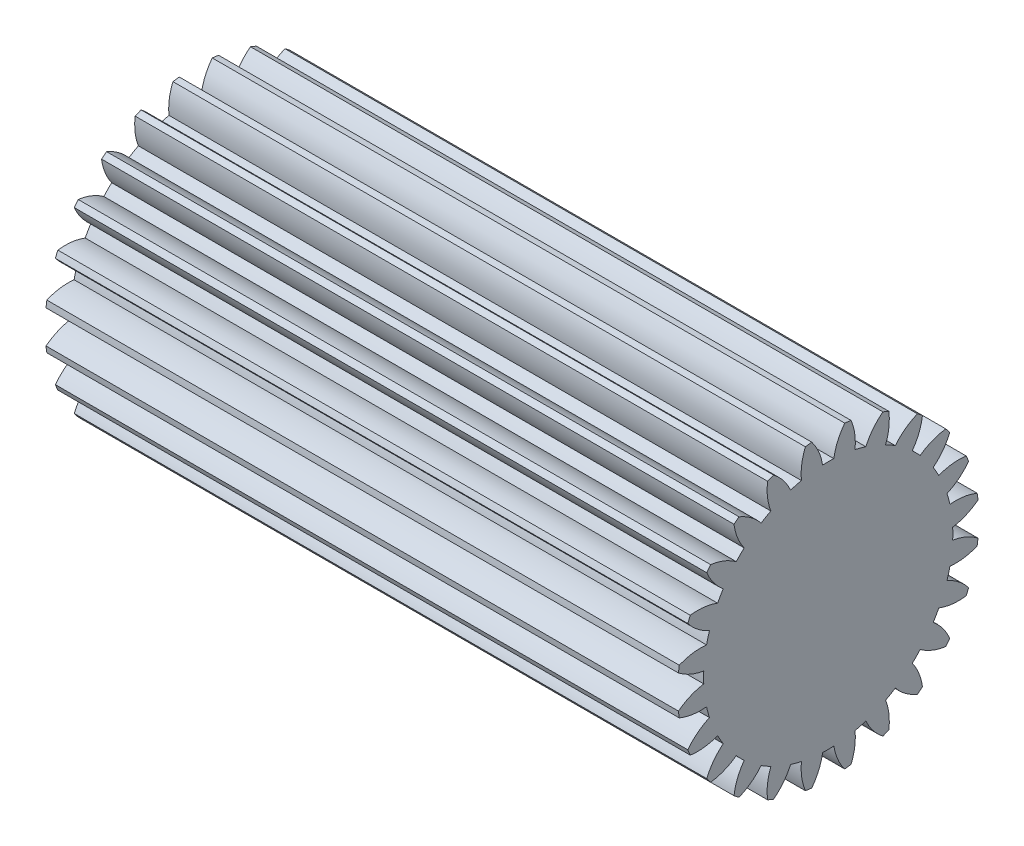
SolidWorks part; units mm, degrees
ref_plane "Plane1" through (0, 0, 0) normal (0, 0, 1) x (1, 0, 0)
ref_plane "Plane2" through (0, 0, 0) normal (0, 1, 0) x (1, 0, 0)
ref_plane "Plane3" through (0, 0, 0) normal (1, 0, 0) x (0, 0, -1)
sketch "HoldingSke" plane through (0, 0, 0) normal (0, 1, 0) x (1, 0, 0)
  line L0 (0, 0) -> (0.9135, -0.4067)
  line L1 (-15, 0) -> (100, 0) construction
  line L2 (0, 0) -> (-2.1039, 2.3779)
  line L3 (0, 0) -> (-11.863, 4.5341)
  line L4 (0, 0) -> (7.8894, 3.5126)
  line L5 (0, 0) -> (-46.8476, -17.4728)
  line L6 (0, 0) -> (-9.9476, -6.7116)
  line L7 (-2.1039, 2.3779) -> (8.6586, 51.2059)
  line L8 (-76.2, 54.61) -> (-76.1, 54.61)
  line L9 (-71.009, 38.7566) -> (-53.1078, 45.2721)
  line L10 (-76.2, 71.12) -> (104.1128, 71.12)
  line L11 (0, 0) -> (-12, 0)
  line L12 (-76.2, 101.6) -> (-76.162, 101.6)
  line L13 (24.9733, 27.94) -> (52.9518, 28.4284)
  line L14 (24.9733, 27.94) -> (24.9743, 27.94)
  line L15 (24.9733, 27.94) -> (100.4006, 29.5858)
  line L16 (-63.627, -1) -> (-12.827, -1)
  circle A0 centre (0, 0) radius 0.4
  circle A1 centre (0, 0) radius 10.749
  circle A2 centre (0, 0) radius 37.5
  circle A3 centre (0, 0) radius 0.4
  dimension "Num_teeth" = 24
  dimension "Pitch_radius" = 180.3128
  dimension "Width" = 12
sketch "BasProSke" plane through (0, 0, 0) normal (0, 1, 0) x (1, 0, 0)
  line L0 (-10, 0) -> (60, 0) construction
  line L1 (0, 0) -> (0, 13)
  line L2 (0, 0) -> (54.565, 0)
  line L3 (54.565, 0) -> (54.565, 13)
  line L4 (54.565, 13) -> (0, 13)
  dimension "Thickness" = 54.565
  dimension "Diameter" = 26
revolve "Base-Revolve" add sketch "BasProSke" angle 360 about L0
sketch "TooCutSke" plane through (0, 0, 0) normal (1, 0, 0) x (0, 0, -1)
  line L1 (0, 0) -> (0, 107) construction
  line L2 (0, 0) -> (-0.8513, 11.9698) construction
  line L3 (0, 0) -> (-3.127, 23.752) construction
  line L4 (-0.8513, 11.9698) -> (-1.5635, 11.876) construction
  arc A0 (0.4834, 10.7381) -> (-0.4834, 10.7381) centre (0, 0) ccw
  arc A1 (1.4409, 12.9455) -> (-1.4409, 12.9455) centre (0, 0) ccw
  circle A2 centre (0, 0) radius 12 construction
  circle A3 centre (0, 0) radius 11.2763 construction
  arc A4 (-0.4834, 10.7381) -> (-1.4409, 12.9455) centre (-5.2252, 9.9926) ccw
  arc A5 (1.4409, 12.9455) -> (0.4834, 10.7381) centre (5.2252, 9.9926) ccw
extrude "ToothCut" cut sketch "TooCutSke" along normal through all
fillet "Breaks" [suppressed] radius 0.02 tangent propagation no
fillet "RootFillets" [suppressed] radius 0.251
pattern_circular "TeethCuts" count 24 every 15 about axis through (-10, 0, 0) along (1, 0, 0) of "ToothCut", "RootFillets", "Breaks"
sketch "HubNeaOneSke" plane through (0, 0, 0) normal (-1, 0, 0) x (0, 0, 1)
  circle A0 centre (0, 0) radius 10.749
  dimension "Diameter" = 21.498
extrude "HubNearOne" [suppressed] add sketch "HubNeaOneSke" along normal blind 15.1851
sketch "HubNeaBotSke" plane through (0, 0, 0) normal (-1, 0, 0) x (0, 0, 1)
  circle A0 centre (0, 0) radius 10.749
  dimension "Diameter" = 21.498
extrude "HubNearBoth" [suppressed] add sketch "HubNeaBotSke" along normal blind 7.5925
ref_plane "FarPln" through (54.565, 0, 0) normal (1, 0, 0) x (0, 0, -1)
sketch "HubFarSke" plane through (54.565, 0, 0) normal (1, 0, 0) x (0, 0, -1)
  circle A0 centre (0, 0) radius 10.749
  dimension "Diameter" = 21.498
extrude "HubFar" [suppressed] add sketch "HubFarSke" along normal blind 7.5925
sketch "BorSke" plane through (0, 0, 0) normal (1, 0, 0) x (0, 0, -1)
  circle A0 centre (0, 0) radius 0.4
  dimension "Diameter" = 0.8
extrude "Bore" cut sketch "BorSke" along normal mid plane 100.0001
sketch "KeySke" plane through (0, 0, 0) normal (1, 0, 0) x (0, 0, -1)
  line L0 (-0.05, 0) -> (-0.05, 0.5)
  line L1 (-0.05, 0.5) -> (0.05, 0.5)
  line L2 (0.05, 0.5) -> (0.05, 0)
  line L3 (0, 0) -> (0, 34) construction
  line L4 (-0.05, 0) -> (0.05, 0)
  dimension "Width" = 0.1
extrude "Keyway" [suppressed] cut sketch "KeySke" along normal mid plane 100.0001
pattern_circular "Keyway2" [suppressed] count 2 every 90 about axis through (-10, 0, 0) along (1, 0, 0) reverse direction yes
scale "Scale1" scale about centroid uniform scaling yes scale factor 2
sketch "Sketch1" plane through (81.8451, 0, 0) normal (1, 0, 0) x (0, 0, -1)
  circle A0 centre (0, 0) radius 23.749 construction
  dimension "D1" = 47.498
scale "Scale2" scale about centroid uniform scaling yes scale factor 0.666667
equation "' \"Module@HoldingSke\" = 6.35"
equation "' \"Num_teeth@HoldingSke\" = 12"
equation "' \"Ap@HoldingSke\" =  20"
equation "' \"Ap@HoldingSke\" = 20"
equation "' \"Width@HoldingSke\" = 0.5 * 25.4"
equation "' \"Hub_dia@HoldingSke\"= 1 * 25.4"
equation "' \"Hub_dia@HoldingSke\" = 1 * 25.4"
equation "' \"Overall_len@HoldingSke\" = 1.0 * 25.4"
equation "' \"Bore@HoldingSke\" = 0.75 * 25.4"
equation "' \"T_dim@HoldingSke\" = 0.1 * 25.4"
equation "' \"Width@KeySke\" = 0.25 * 25.4"
equation "' \"Show_teeth@HoldingSke\" = 13"
equation "' \"Backlash@HoldingSke\" = 0.009 * 25.4"
equation "' \"Addendum_fac@HoldingSke\" = 1.0"
equation "' \"Dedendum_fac@HoldingSke\" = 1.25"
equation "' \"Dedendum_add@HoldingSke\" = 0.00005 * 25.4"
equation "' \"Clearance_fac@HoldingSke\" = 0.25"
equation "\"Pitch@HoldingSke\" = 1 / \"Module@HoldingSke\""
equation "\"Overcut_dia@TooCutSke\" = (\"Num_teeth@HoldingSke\" + 2 * \"Addendum_fac@HoldingSke\") / \"Pitch@HoldingSke\" + 0.002 * 25.4"
equation "\"Pitch_dia@TooCutSke\" = \"Num_teeth@HoldingSke\" / \"Pitch@HoldingSke\""
equation "\"Base_dia@TooCutSke\" = \"Num_teeth@HoldingSke\" / \"Pitch@HoldingSke\" * cos((\"Ap@HoldingSke\"  * 3.14159265 / 180))"
equation "\"Root_dia@TooCutSke\" = (\"Num_teeth@HoldingSke\" + 2) / \"Pitch@HoldingSke\" - 2 * (\"Addendum_fac@HoldingSke\" + \"Dedendum_fac@HoldingSke\") / \"Pitch@HoldingSke\" - \"Dedendum_add@HoldingSke\" * 2"
equation "\"Half_ang@TooCutSke\" = 180 / \"Num_teeth@HoldingSke\""
equation "\"Half_CT@TooCutSke\" = \"Num_teeth@HoldingSke\" / \"Pitch@HoldingSke\" * sin((3.14159265 / 2 / \"Num_teeth@HoldingSke\")) / 2 - 7 * \"Backlash@HoldingSke\" / 4"
equation "\"Flank_rad@TooCutSke\" = \"Num_teeth@HoldingSke\" / \"Pitch@HoldingSke\" / 5"
equation "\"Radius@RootFillets\" = \"Clearance_fac@HoldingSke\" / \"Pitch@HoldingSke\" + \"Dedendum_add@HoldingSke\""
equation "\"Break_rad@Breaks\" = 0.02 / \"Pitch@HoldingSke\""
equation "\"Thickness@HoldingSke\" = \"Width@HoldingSke\""
equation "\"OAL@HoldingSke\" = \"Thickness@HoldingSke\""
equation "\"MHD@HoldingSke\" = (\"Num_teeth@HoldingSke\" + 2) / \"Pitch@HoldingSke\" - 2 * (\"Addendum_fac@HoldingSke\" + \"Dedendum_fac@HoldingSke\")  / \"Pitch@HoldingSke\" - \"Dedendum_add@HoldingSke\" * 2"
equation "\"MBD@HoldingSke\" = (\"Num_teeth@HoldingSke\" + 2) / \"Pitch@HoldingSke\" - 2 * (\"Addendum_fac@HoldingSke\" + \"Dedendum_fac@HoldingSke\")  / \"Pitch@HoldingSke\" - \"Dedendum_add@HoldingSke\" * 2 - 0.002 * 25.4"
equation "\"MHD@HoldingSke\" = ((sgn( \"MHD@HoldingSke\" - \"Hub_dia@HoldingSke\" )-1)*( \"MHD@HoldingSke\" - \"Hub_dia@HoldingSke\" ))/-2+ \"Hub_dia@HoldingSke\""
equation "\"MBD@HoldingSke\" = ((sgn( \"MBD@HoldingSke\" - \"Bore@HoldingSke\" )-1)*( \"MBD@HoldingSke\" - \"Bore@HoldingSke\" ))/-2+ \"Bore@HoldingSke\""
equation "\"OAL@HoldingSke\" = ((sgn( \"OAL@HoldingSke\" - \"Overall_len@HoldingSke\" )+1)*( \"OAL@HoldingSke\" - \"Overall_len@HoldingSke\" ))/2 + \"Overall_len@HoldingSke\" + 0.000002 * 25.4"
equation "\"Num_teeth@TeethCuts\" = int( \"Show_teeth@HoldingSke\" ) + 1"
equation "\"Num_teeth@TeethCuts\" = ((sgn( \"Num_teeth@TeethCuts\" - \"Num_teeth@HoldingSke\" )-1)*( \"Num_teeth@TeethCuts\" - \"Num_teeth@HoldingSke\" ))/-2+ \"Num_teeth@HoldingSke\""
equation "\"Num_teeth@TeethCuts\" = ((sgn( \"Num_teeth@TeethCuts\" - 2.0)+1)*( \"Num_teeth@TeethCuts\" - 2.0))/2 +2.0"
equation "\"Angle@TeethCuts\" = 360.0 / \"Num_teeth@HoldingSke\""
equation "\"Diameter@BasProSke\" = (\"Num_teeth@HoldingSke\" + 2 * \"Addendum_fac@HoldingSke\") / \"Pitch@HoldingSke\""
equation "' \"Fillet_rad@BasProSke\" =  \"Thickness@HoldingSke\" * 0.05"
equation "' \"Fillet_rad@BasProSke\" = \"Thickness@HoldingSke\" * 0.05"
equation "\"MHD@HoldingSke\" = ((sgn( \"MHD@HoldingSke\" - \"Root_dia@TooCutSke\" )-1)*( \"MHD@HoldingSke\" - \"Root_dia@TooCutSke\" ))/-2+ \"Root_dia@TooCutSke\""
equation "\"Diameter@HubNeaOneSke\" = \"MHD@HoldingSke\""
equation "\"Length@HubNearOne\" = \"OAL@HoldingSke\" - \"Thickness@BasProSke\""
equation "\"Diameter@HubNeaBotSke\" = \"MHD@HoldingSke\""
equation "\"Length@HubNearBoth\" = ( \"OAL@HoldingSke\" - \"Thickness@BasProSke\" ) / 2.0"
equation "\"Thickness@FarPln\" = \"Thickness@BasProSke\""
equation "\"Diameter@HubFarSke\" = \"MHD@HoldingSke\""
equation "\"Length@HubFar\" = ( \"OAL@HoldingSke\" - \"Thickness@BasProSke\" ) / 2.0"
equation "\"Diameter@BorSke\" = \"MBD@HoldingSke\""
equation "\"D1@Bore\" = \"OAL@HoldingSke\" * 2.0"
equation "\"D1@Keyway\" = \"OAL@HoldingSke\" * 2.0"
equation "\"Offset@KeySke\" = \"T_dim@HoldingSke\" + \"MBD@HoldingSke\" / 2.0"
